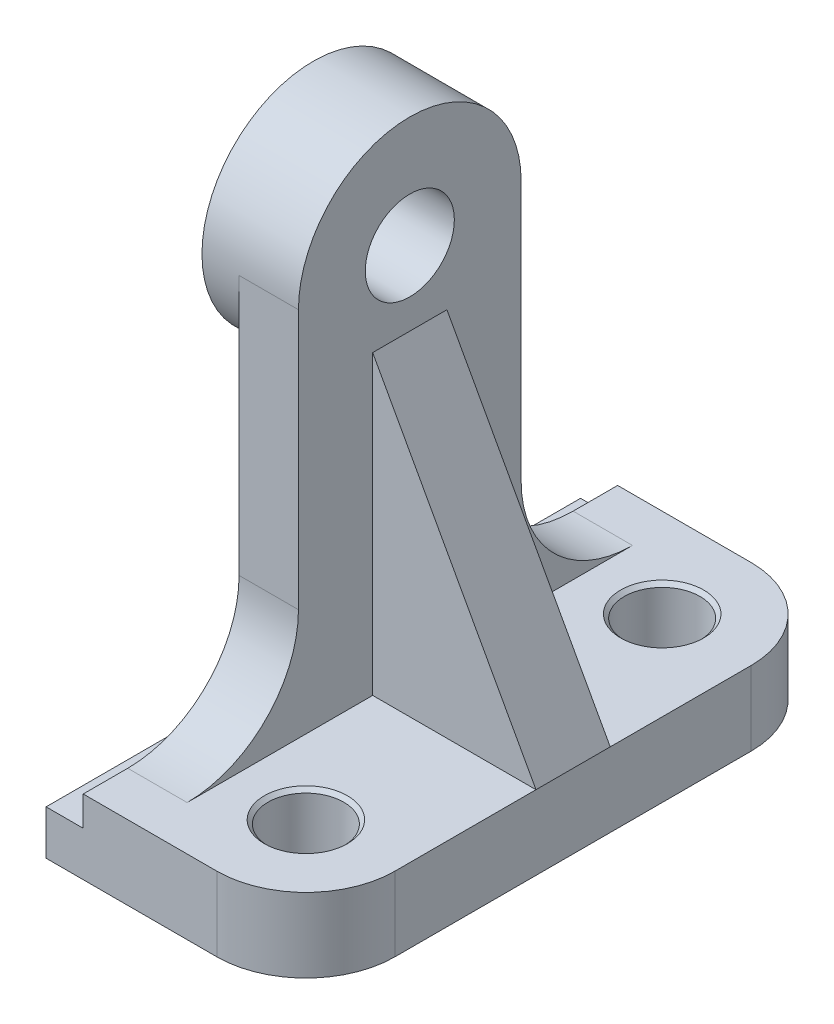
SolidWorks part; units mm, degrees
ref_plane "Front Plane" through (0, 0, 0) normal (0, 0, 1) x (1, 0, 0)
ref_plane "Top Plane" through (0, 0, 0) normal (0, 1, 0) x (1, 0, 0)
ref_plane "Right Plane" through (0, 0, 0) normal (1, 0, 0) x (0, 0, -1)
sketch "Sketch3" plane through (0, 0, 0) normal (0, 0, 1) x (1, 0, 0)
  line L0 (0, 42.825) -> (0, -44.5435) construction
  line L1 (-50.2769, 0) -> (54.0134, 0) construction
  line L2 (0, 0) -> (0, 40)
  line L3 (0, 0) -> (22, 0)
  line L4 (0, 40) -> (22, 0)
  dimension "D1" = 40
  dimension "D2" = 22
extrude "Boss-Extrude3" add sketch "Sketch3" along normal mid plane 10 separate body
sketch "Sketch4" plane through (0, 0, 0) normal (0, 0, 1) x (1, 0, 0)
  line L0 (22, 0) -> (-8, 0)
  line L1 (-8, 0) -> (-8, -4)
  line L2 (-8, -4) -> (-13, -4)
  line L3 (22, 0) -> (22, -10)
  line L4 (22, -10) -> (-13, -10)
  line L5 (-13, -10) -> (-13, -4)
  dimension "D1" = 35
  dimension "D2" = 4
  dimension "D3" = 10
  dimension "D4" = 5
extrude "Boss-Extrude4" add sketch "Sketch4" along normal mid plane 72 separate body
sketch "Sketch5" plane through (0, 0, 0) normal (1, 0, 0) x (0, 0, -1)
  line L0 (0, 62.8114) -> (0, -17.3556) construction
  line L1 (5, 0) -> (36, 0) construction
  line L2 (-30, 0) -> (30, 0)
  line L3 (-15, 50) -> (-15, 15)
  line L4 (15, 50) -> (15, 15)
  line L6 (-36, 0) -> (-5, 0) construction
  circle A2 centre (0, 50) radius 6
  arc A3 (15, 50) -> (-15, 50) centre (0, 50) ccw
  arc A4 (-30, 0) -> (-15, 15) centre (-30, 15) ccw
  arc A5 (15, 15) -> (30, 0) centre (30, 15) ccw
  dimension "D1" = 12
  dimension "D2" = 15
  dimension "D3" = 15
  dimension "D4" = 15
  dimension "D5" = 50
extrude "Boss-Extrude5" add sketch "Sketch5" against normal blind 8 separate body
sketch "Sketch6" plane through (-8, 0, 0) normal (-1, 0, 0) x (0, 0, 1)
  line L0 (0, 70.7286) -> (0, -20.2374) construction
  line L1 (-49.3068, 0) -> (54.9419, 0) construction
  circle A0 centre (0, 50) radius 6
  circle A1 centre (0, 50) radius 15
extrude "Boss-Extrude6" add sketch "Sketch6" along normal blind 5 separate body
fillet "Fillet1" radius 12 2 edges at (22, -5, 36) (22, -5, -36)
sketch "Sketch8" plane through (0, 0, 0) normal (0, 1, 0) x (1, 0, 0)
  line L0 (0, 0) -> (32.1347, 0) construction
  line L1 (10, 24) -> (10, 0) construction
  line L2 (10, 0) -> (10, -24) construction
  line L3 (0, 39.8341) -> (0, -43.4294) construction
  circle A1 centre (10, 24) radius 5.1
  circle A2 centre (10, -24) radius 5.1
  point P10 (0, 0)
  dimension "D1" = 10.2
  dimension "D2" = 10.2
  dimension "D3" = 48
  dimension "D4" = 20
  dimension "D5" = 24
extrude "Cut-Extrude1" cut sketch "Sketch8" against normal through all
chamfer "Chamfer1" distance 0.5 angle 45 2 edges at (4.9, 0, -24) (4.9, 0, 24)
